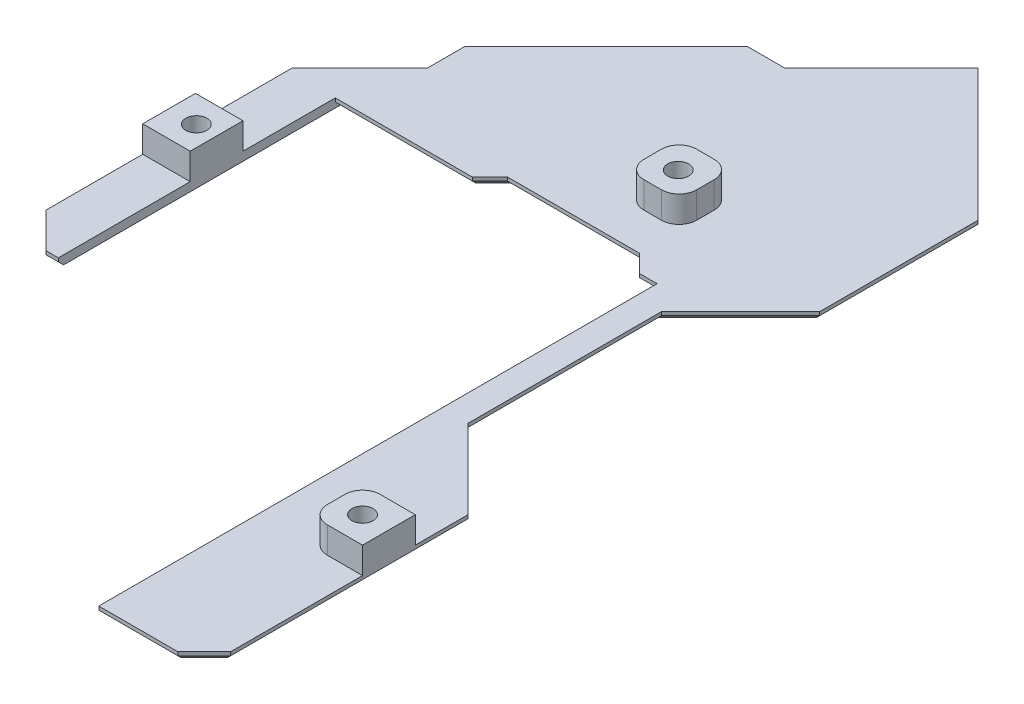
SolidWorks part; units mm, degrees
ref_plane "前视基准面" through (0, 0, 0) normal (0, 0, 1) x (1, 0, 0)
ref_plane "上视基准面" through (0, 0, 0) normal (0, 1, 0) x (1, 0, 0)
ref_plane "右视基准面" through (0, 0, 0) normal (1, 0, 0) x (0, 0, -1)
sketch "草图1" plane through (0, 0, 0) normal (0, 1, 0) x (1, 0, 0)
  line L0 (-54, 36) -> (-44, 26) construction
  line L1 (-3, 0) -> (-12, 0)
  line L2 (0, 3) -> (0, 30.0029)
  line L5 (-54, 47) -> (-54, 36) construction
  line L7 (-54, 64) -> (-54, 53) construction
  line L8 (-46.3, 71.7) -> (-54, 64) construction
  line L9 (-46.3, 75.9426) -> (-46.3, 71.7) construction
  line L10 (-30.2426, 92) -> (-46.3, 75.9426) construction
  line L11 (-26, 92) -> (-30.2426, 92) construction
  line L12 (-15, 103) -> (-26, 92) construction
  line L13 (0, 88) -> (-15, 103) construction
  line L14 (-54, 36) -> (-50, 32)
  line L15 (-54, 47) -> (-54, 36)
  line L16 (-54, 53) -> (-54, 47)
  line L17 (-54, 64) -> (-54, 53)
  line L18 (-46.3, 71.7) -> (-54, 64)
  line L19 (-46.3, 75.9426) -> (-46.3, 71.7)
  line L20 (-30.2426, 92) -> (-46.3, 75.9426)
  line L21 (-26, 92) -> (-30.2426, 92)
  line L22 (-15, 103) -> (-26, 92)
  line L23 (0, 88) -> (-15, 103)
  line L26 (0, 69.9971) -> (-9, 60.9971)
  line L27 (-9, 60.9971) -> (-9, 39.0029)
  line L28 (-9, 39.0029) -> (0, 30.0029)
  line L31 (-3.4, 64.9) -> (-8, 60.3) construction
  line L33 (-8, 39.7) -> (-3.4, 35.1) construction
  line L36 (0, 69.9971) -> (0, 88)
  line L37 (-12, 63.5) -> (-12, 0)
  line L38 (-13.1, 9) -> (-13.1, 62.5) construction
  line L39 (0, 3) -> (-3, 0) construction
  line L40 (0, 3) -> (-3, 0)
  line L41 (-12, 63.5) -> (-48.6, 63.5)
  line L42 (-48.6, 63.5) -> (-48.6, 32)
  line L43 (-48.6, 32) -> (-50, 32)
  line L44 (-47.6, 53.1) -> (-47.6, 62.5) construction
  line L45 (-47.6, 62.5) -> (-44.2, 62.5) construction
  line L46 (-8, 60.3) -> (-8, 39.7) construction
  dimension "D1" = 31.5
  dimension "D3" = 1.2
  dimension "D4" = 1
  dimension "D5" = 1.2
  dimension "D7" = 1.1
  dimension "D8" = 1
  dimension "D9" = 1
extrude "凸台-拉伸1" add sketch "草图1" along normal blind 1
sketch "草图2" plane through (0, 1, 0) normal (0, 1, 0) x (1, 0, 0)
  line L0 (-48.6, 32) -> (-48.6, 63.5) construction
  line L1 (-48.6, 47) -> (-48.6, 53)
  line L2 (-50, 53) -> (-48.6, 53)
  line L3 (-50, 47) -> (-48.6, 47)
  line L4 (-4, 18) -> (0, 18)
  line L5 (-6, 22) -> (-6, 20)
  line L6 (0, 24) -> (-4, 24)
  line L7 (0, 18) -> (0, 24)
  line L8 (-4, 18) -> (0, 18)
  line L9 (-6, 22) -> (-6, 20)
  line L10 (0, 24) -> (-4, 24)
  line L11 (0, 18) -> (0, 24)
  line L12 (-48, 49) -> (-48, 51)
  line L13 (-54, 47) -> (-50, 47)
  line L14 (-54, 53) -> (-54, 47)
  line L15 (-50, 53) -> (-54, 53)
  line L17 (-54, 47) -> (-50, 47)
  line L18 (-54, 53) -> (-54, 47)
  line L19 (-50, 53) -> (-54, 53)
  line L20 (-22, 74) -> (-22, 72)
  line L21 (-18, 76) -> (-20, 76)
  line L22 (-16, 72) -> (-16, 74)
  line L23 (-20, 70) -> (-18, 70)
  line L24 (-22, 74) -> (-22, 72)
  line L25 (-18, 76) -> (-20, 76)
  line L26 (-16, 72) -> (-16, 74)
  line L27 (-20, 70) -> (-18, 70)
  arc A2 (-6, 20) -> (-4, 18) centre (-4, 20) ccw
  arc A3 (-4, 24) -> (-6, 22) centre (-4, 22) ccw
  arc A4 (-6, 20) -> (-4, 18) centre (-4, 20) ccw
  arc A5 (-4, 24) -> (-6, 22) centre (-4, 22) ccw
  arc A6 (-50, 47) -> (-48, 49) centre (-50, 49) ccw
  arc A7 (-48, 51) -> (-50, 53) centre (-50, 51) ccw
  arc A12 (-20, 76) -> (-22, 74) centre (-20, 74) ccw
  arc A13 (-16, 74) -> (-18, 76) centre (-18, 74) ccw
  arc A14 (-18, 70) -> (-16, 72) centre (-18, 72) ccw
  arc A15 (-22, 72) -> (-20, 70) centre (-20, 72) ccw
  arc A16 (-20, 76) -> (-22, 74) centre (-20, 74) ccw
  arc A17 (-16, 74) -> (-18, 76) centre (-18, 74) ccw
  arc A18 (-18, 70) -> (-16, 72) centre (-18, 72) ccw
  arc A19 (-22, 72) -> (-20, 70) centre (-20, 72) ccw
  dimension "D1" = 0
  dimension "D2" = 0
  dimension "D3" = 0
extrude "凸台-拉伸2" add sketch "草图2" along normal blind 3
sketch "草图3" plane through (0, 0, 0) normal (0, -1, 0) x (1, 0, 0)
  circle A0 centre (-19, -72.9) radius 1.2 construction
  circle A1 centre (-50.9, -50) radius 1.2 construction
  circle A2 centre (-3, -21) radius 1.2 construction
  circle A3 centre (-19, -72.9) radius 1.2
  circle A4 centre (-50.9, -50) radius 1.2
  circle A5 centre (-3, -21) radius 1.2
extrude "切除-拉伸1" cut sketch "草图3" against normal through all
sketch "草图4" plane through (0, 0, 0) normal (0, -1, 0) x (1, 0, 0)
  circle A2 centre (-19, -72.9) radius 2.05 construction
  circle A3 centre (-50.9, -50) radius 2.05 construction
  circle A4 centre (-19, -72.9) radius 2.05
  circle A5 centre (-50.9, -50) radius 2.05
  circle A8 centre (-3, -21) radius 2.05 construction
  circle A9 centre (-3, -21) radius 2.05
extrude "切除-拉伸2" cut sketch "草图4" against normal blind 2
sketch "草图6" plane through (0, 0, 0) normal (0, -1, 0) x (1, 0, 0)
  line L0 (-16, -65.5) -> (-31, -65.5)
  line L1 (-48.6, -63.5) -> (-12, -63.5) construction
  line L4 (-16, -67.9) -> (-16, -62.5)
  line L5 (-16, -62.5) -> (-31, -62.5)
  line L6 (-31, -62.5) -> (-31, -67.9)
  line L7 (-31, -67.9) -> (-16, -67.9)
  line L8 (-16, -65.5) -> (-16, -62.5)
  line L9 (-16, -62.5) -> (-31, -62.5)
  line L10 (-31, -62.5) -> (-31, -65.5)
  dimension "D2" = 2
  dimension "D1" = 0
extrude "切除-拉伸3" cut sketch "草图6" against normal through all
chamfer "倒角2" distance 2 angle 45 2 edges at (-31, 0.5, -63.5) (-16, 0.5, -63.5)
chamfer "倒角1" distance 0.6 angle 45 22 edges at (-7.5, 0, 0) (-1.5, 0, -1.5) (0, 0, -16.5015) (-4.5, 0, -34.5029) (-9, 0, -50) (-4.5, 0, -65.4971) (0, 0, -78.9985) (-7.5, 0, -95.5) (-20.5, 0, -97.5) (-28.1213, 0, -92) (-38.2713, 0, -83.9713) (-46.3, 0, -73.8213) (-50.15, 0, -67.85) (-54, 0, -50) (-52, 0, -34) (-49.3, 0, -32) (-12, 0, -31.75) (-40.8, 0, -63.5) (-32, 0, -64.5) (-23.5, 0, -65.5) (-15, 0, -64.5) (-13, 0, -63.5)
